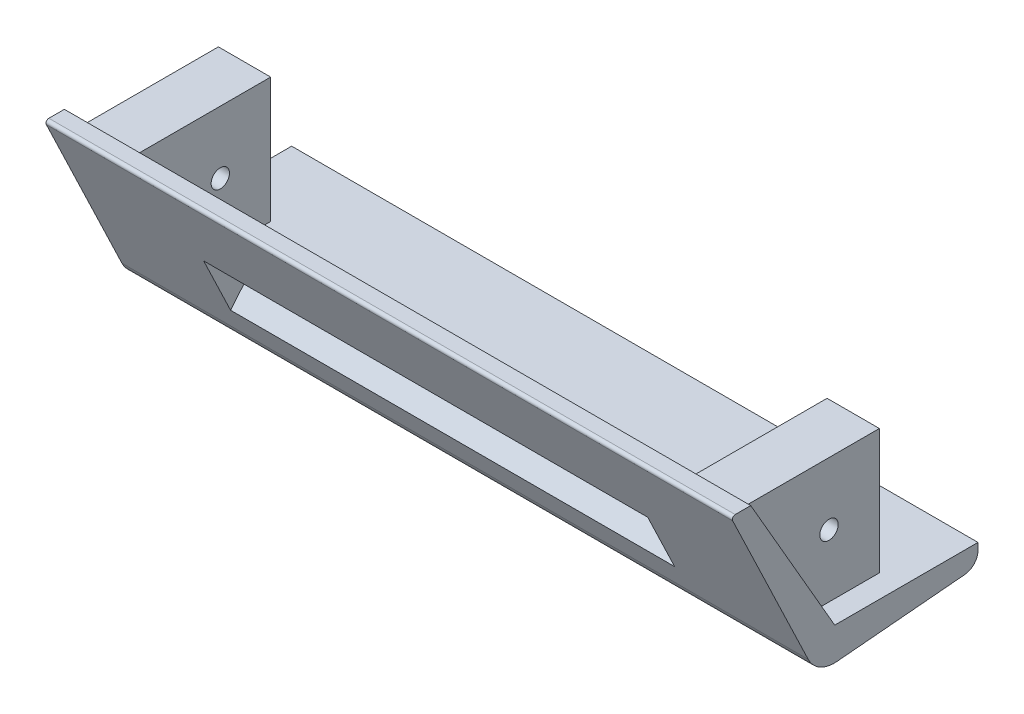
SolidWorks part; units mm, degrees
ref_plane "Front Plane" through (0, 0, 0) normal (0, 0, 1) x (1, 0, 0)
ref_plane "Top Plane" through (0, 0, 0) normal (0, 1, 0) x (1, 0, 0)
ref_plane "Right Plane" through (0, 0, 0) normal (1, 0, 0) x (0, 0, -1)
sketch "Sketch1" plane through (0, 0, 0) normal (1, 0, 0) x (0, 0, -1)
  line L0 (0, 0) -> (-29.3294, 50.8)
  line L1 (0, 0) -> (50, 0)
  line L2 (-29.3294, 50.8) -> (-36.3294, 50.8)
  line L3 (-36.3294, 50.8) -> (-6.2529, -12)
  line L4 (-6.2529, -12) -> (50, -7)
  line L5 (50, -7) -> (50, 0)
  line L6 (-6.2529, -12) -> (-6.2529, 0) construction
  line L7 (-12, 0) -> (0, 0) construction
  dimension "D1" = 50
  dimension "D2" = 60
  dimension "D3" = 50.8
  dimension "D4" = 7
  dimension "D5" = 7
  dimension "D6" = 12
extrude "Boss-Extrude2" add sketch "Sketch1" along normal mid plane 239.55
sketch "Sketch2" plane through (0, 0, 0) normal (0, 0, 1) x (1, 0, 0)
  line L0 (0, 0) -> (0, 50.8) construction
  line L5 (115.75, 47.625) -> (96.7, 47.625) construction
  line L6 (115.75, 47.625) -> (115.75, 3.175) construction
  line L11 (115.75, 3.175) -> (96.7, 3.175) construction
  line L12 (96.7, 47.625) -> (96.7, 3.175) construction
  line L14 (115.35, 47.225) -> (115.35, 3.575)
  line L15 (115.35, 3.575) -> (97.1, 3.575)
  line L28 (97.1, 47.225) -> (97.1, 3.575)
  line L29 (115.35, 47.225) -> (97.1, 47.225)
  line L30 (-96.7, 47.625) -> (-96.7, 3.175) construction
  line L31 (-115.75, 3.175) -> (-96.7, 3.175) construction
  line L32 (-115.75, 47.625) -> (-115.75, 3.175) construction
  line L33 (-115.75, 47.625) -> (-96.7, 47.625) construction
  line L34 (-115.35, 47.225) -> (-97.1, 47.225)
  line L35 (-97.1, 47.225) -> (-97.1, 3.575)
  line L36 (-115.35, 3.575) -> (-97.1, 3.575)
  line L37 (-115.35, 47.225) -> (-115.35, 3.575)
  line L39 (119.775, 0) -> (-119.775, 0) construction
  line L40 (119.775, 50.8) -> (-119.775, 50.8) construction
  line L41 (119.775, 0) -> (119.775, 50.8) construction
  dimension "D2" = 19.05
  dimension "D3" = 44.45
  dimension "D6" = 3.175
  dimension "D4" = 3.175
  dimension "D7" = 4.025
  dimension "D1" = 193.4
  dimension "D5" = 0.4
extrude "Boss-Extrude1" add sketch "Sketch2" along normal up to surface and the other way blind 20 up to face at (0, 25.4, 14.6647)
sketch "Sketch4" plane through (0, 0, 0) normal (1, 0, 0) x (0, 0, -1)
  line L1 (-23, 22.9681) -> (-15.6955, 27.1854)
  line L2 (-36.3294, 50.8) -> (-6.2529, -12) construction
  line L3 (0, 0) -> (-29.3294, 50.8) construction
  line L4 (-15.6955, 27.1854) -> (-6.6955, 11.5969)
  line L5 (-6.6955, 11.5969) -> (-13.6084, 3.3584)
  line L8 (-23, 22.9681) -> (-13.6084, 3.3584)
  dimension "D1" = 18
  dimension "D2" = 23
  dimension "D3" = 110
extrude "Cut-Extrude2" cut sketch "Sketch4" against normal mid plane 155
fillet "Fillet1" radius 10 1 edges at (0, -12, 6.2529)
fillet "Fillet2" radius 5 1 edges at (0, -7, -50)
fillet "Fillet3" radius 1 1 edges at (0, 50.8, 36.3294)
sketch "Sketch8" plane through (77.5, 0, 0) normal (-1, 0, 0) x (0, 0, 1)
  line L0 (15.6955, 27.1854) -> (18.2936, 25.6854)
  line L1 (15.6955, 27.1854) -> (23, 22.9681) construction
  line L2 (18.2936, 25.6854) -> (10.2936, 11.829)
  line L3 (7.5615, 11.0969) -> (6.6955, 11.5969)
  line L4 (6.6955, 11.5969) -> (15.6955, 27.1854) construction
  line L5 (15.6955, 27.1854) -> (6.6955, 11.5969)
  arc A0 (10.2936, 11.829) -> (7.5615, 11.0969) centre (8.5615, 12.829) cw
  dimension "D2" = 2
  dimension "D1" = 3
extrude "Cut-Extrude3" cut sketch "Sketch8" against normal blind 10
hole_wizard "M6 Clearance Hole1" positions "Sketch11" profile "Sketch10" hole size "M6" standard "ANSI Metric" end condition through all
sketch "Sketch11" plane through (115.35, 0, 0) normal (1, 0, 0) x (0, 0, -1)
  point P0 (2.4206, 25.4)
sketch "Sketch10" plane through (115.35, 25.4, -2.4206) normal (0, 1, 0) x (0, 0, -1)
  line L0 (0, 0) -> (0, 235.125)
  line L1 (0, 235.125) -> (3.2, 235.125)
  line L2 (3.2, 235.125) -> (3.2, 0)
  line L5 (3.2, 0) -> (0, 0)
  line L11 (0, -6.35) -> (0, 107.95) construction
  dimension "Thru Hole Dia." = 6.4
  dimension "Thru Hole Depth" = 235.125
equation "\"D1@Sketch2\"=187.05mm+0.25in"
equation "\"RailSpacing\"= 188.75mm"
equation "\"D1@Boss-Extrude2\"=\"RailSpacing\"+2in"
